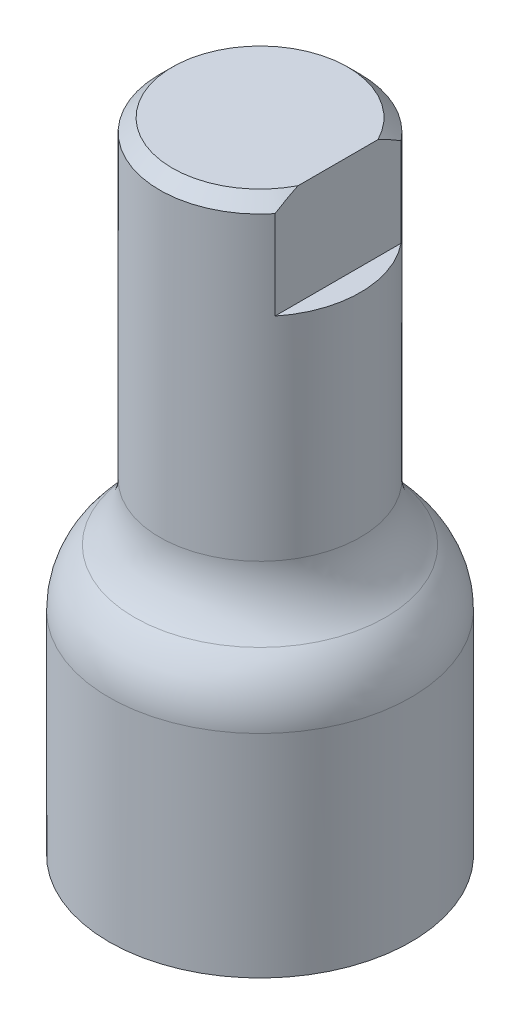
SolidWorks part; units mm, degrees
ref_plane "Front" through (0, 0, 0) normal (0, 0, 1) x (1, 0, 0)
ref_plane "Top" through (0, 0, 0) normal (0, 1, 0) x (-1, 0, 0)
ref_plane "Right" through (0, 0, 0) normal (1, 0, 0) x (0, 0, -1)
sketch "Sketch1" plane through (0, 0, 0) normal (0, 1, 0) x (-1, 0, 0)
  circle A0 centre (0, 0) radius 6.2865
  dimension "D1" = 12.573
extrude "Base-Extrude" add sketch "Sketch1" along normal blind 40
sketch "Sketch3" plane through (0, 0, 0) normal (0, 1, 0) x (-1, 0, 0)
  circle A1 centre (0, 0) radius 9.4615
  circle A2 centre (0, 0) radius 9.4615
  dimension "D1" = 3.175
extrude "Boss-Extrude1" add sketch "Sketch3" along normal blind 15.875
sketch "Sketch4" plane through (0, 0, 0) normal (0, 1, 0) x (-1, 0, 0)
  line L0 (-4.8895, 4.2479) -> (-4.8895, -4.2479) construction
  circle A0 centre (0, 0) radius 6.35
  arc A1 (-4.8895, -4.2479) -> (-4.8895, 4.2479) centre (0, 0) ccw construction
  dimension "D2" = 6.477
  dimension "D3" = 6.477
  dimension "D4" = 12.7
  dimension "D1" = 1.5875
extrude "Cut-Extrude1" cut sketch "Sketch4" along normal blind 12.7
fillet "Fillet1" radius 4.7625 1 edges at (0, 15.875, 6.2865)
fillet "Fillet2" radius 4.7625 1 edges at (0, 15.875, 9.4615)
sketch "Sketch5" [suppressed] plane through (4.8895, 0, 0) normal (-1, 0, 0) x (0, 0, 1)
  line L0 (4.2479, 0) -> (-4.2479, 0) construction
  circle A0 centre (0, 6.35) radius 1.1906
  dimension "D2" = 2.3813
  dimension "D1" = 6.35
extrude "Cut-Extrude2" [suppressed] cut sketch "Sketch5" against normal through all
sketch "Sketch7" plane through (0, 40, 0) normal (0, 1, 0) x (-1, 0, 0)
  line L1 (-4.8895, 3.9513) -> (-4.8895, -3.9513)
  circle A1 centre (0, 0) radius 6.2865 construction
  arc A2 (-4.8895, 3.9513) -> (-4.8895, -3.9513) centre (0, 0) ccw
extrude "Cut-Extrude3" cut sketch "Sketch7" against normal blind 6.35
chamfer "Chamfer1" distance 0.7937 angle 45 1 edges at (-6.2865, 40, 0)
